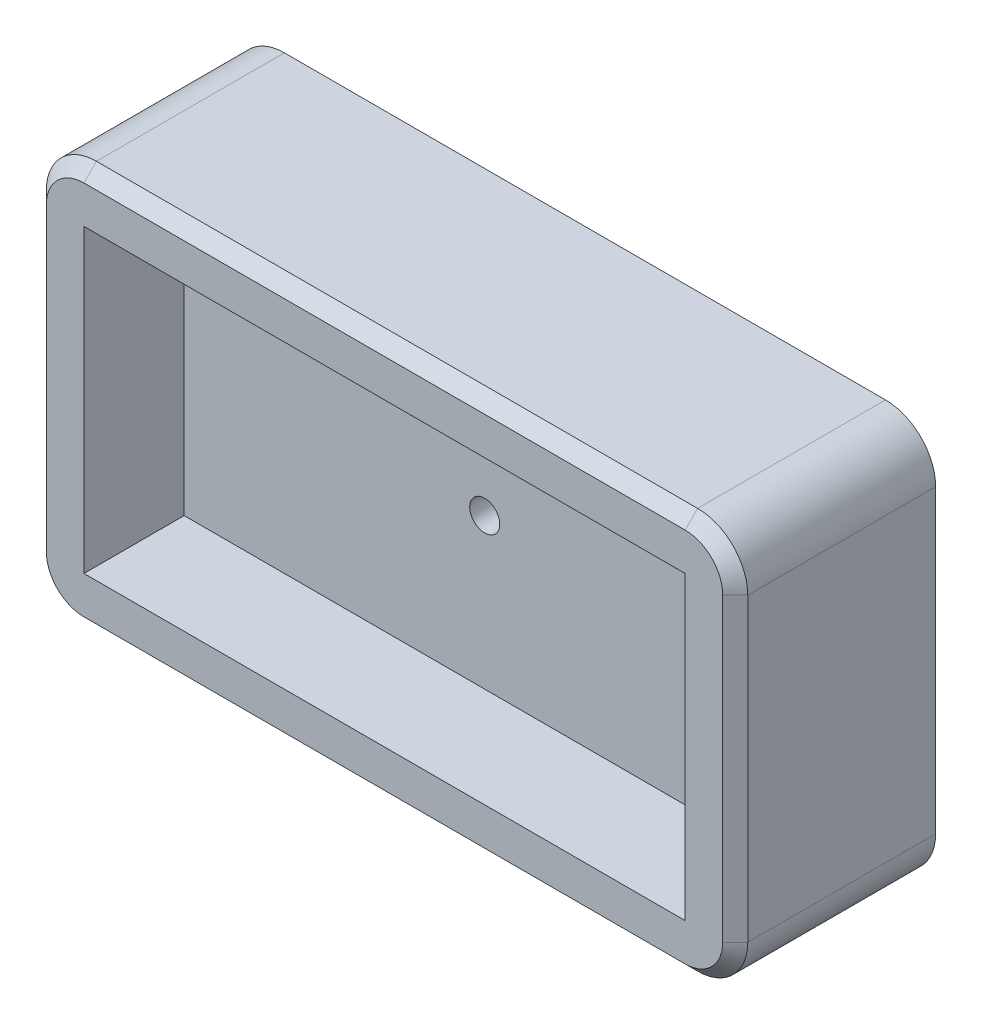
SolidWorks part; units mm, degrees
ref_plane "Front Plane" through (0, 0, 0) normal (0, 0, 1) x (1, 0, 0)
ref_plane "Top Plane" through (0, 0, 0) normal (0, 1, 0) x (1, 0, 0)
ref_plane "Right Plane" through (0, 0, 0) normal (1, 0, 0) x (0, 0, -1)
sketch "Sketch2" plane through (0, 0, 0) normal (0, 0, 1) x (1, 0, 0)
  line L0 (-38.1, 25.4) -> (38.1, 25.4)
  line L1 (-38.1, -19.05) -> (38.1, -19.05)
  line L2 (-38.1, -19.05) -> (-38.1, 19.05)
  line L3 (-38.1, 19.05) -> (38.1, 19.05)
  line L4 (38.1, -19.05) -> (38.1, 19.05)
  line L5 (-38.1, -19.05) -> (38.1, 19.05) construction
  line L6 (-38.1, 19.05) -> (38.1, -19.05) construction
  line L7 (44.45, -19.05) -> (44.45, 19.05)
  line L8 (-38.1, -25.4) -> (38.1, -25.4)
  line L9 (-44.45, -19.05) -> (-44.45, 19.05)
  line L10 (-44.45, -25.4) -> (44.45, -25.4) construction
  line L11 (-44.45, -25.4) -> (-44.45, 25.4) construction
  line L12 (44.45, -25.4) -> (44.45, 25.4) construction
  line L13 (-44.45, 25.4) -> (44.45, 25.4) construction
  arc A0 (-38.1, -25.4) -> (-44.45, -19.05) centre (-38.1, -19.05) cw
  arc A1 (44.45, -19.05) -> (38.1, -25.4) centre (38.1, -19.05) cw
  arc A2 (38.1, 25.4) -> (44.45, 19.05) centre (38.1, 19.05) cw
  arc A3 (-38.1, 25.4) -> (-44.45, 19.05) centre (-38.1, 19.05) ccw
  point P0 (0, 0)
  dimension "D4" = 6.35
  dimension "D1" = 76.2
  dimension "D2" = 38.1
  dimension "D3" = 6.35
extrude "Boss-Extrude1" add sketch "Sketch2" against normal blind 12.7 contours L1 L4 L3 L2 | L0 A3 L9 A0 L8 A1 L7 A2 L4 L1 L2 L3 region at (0, 24.3761, 0) region at (0, 0, 0)
extrude "Boss-Extrude2" add sketch "Sketch2<3>" along normal blind 12.7
sketch "Sketch2<3>" plane through (0, 0, 0) normal (0, 0, 1) x (1, 0, 0) same geometry as "Sketch2"
chamfer "Chamfer1" distance 1.5875 angle 45 8 edges at (44.45, 0, 12.7) (42.5901, 23.5401, 12.7) (42.5901, -23.5401, 12.7) (0, 25.4, 12.7) (0, -25.4, 12.7) (-42.5901, 23.5401, 12.7) (-42.5901, -23.5401, 12.7) (-44.45, 0, 12.7)
sketch "Sketch3" plane through (0, 0, -12.7) normal (0, 0, -1) x (-1, 0, 0)
  circle A0 centre (0, 0) radius 1.905
  dimension "D1" = 3.81
extrude "Cut-Extrude1" cut sketch "Sketch3" against normal through all
